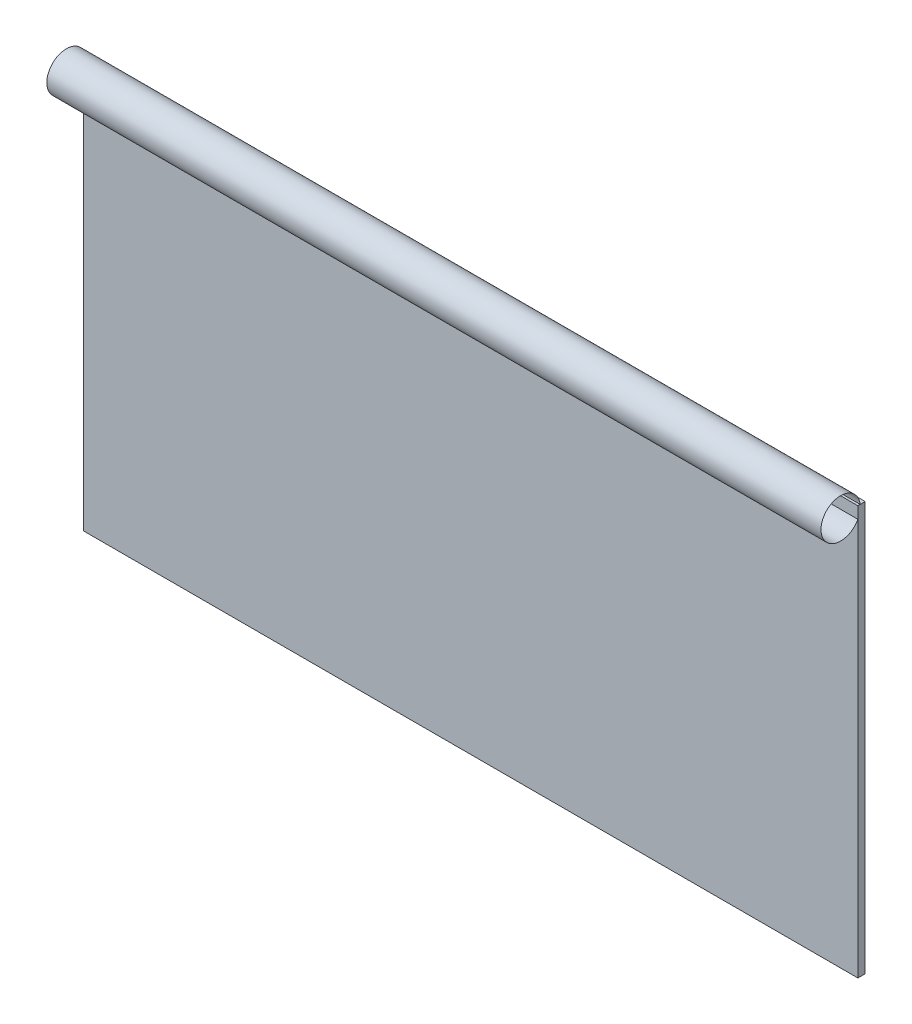
SolidWorks part; units mm, degrees
material "201 Annealed Stainless Steel (SS)"
ref_plane "Front Plane" through (0, 0, 0) normal (0, 0, 1) x (1, 0, 0)
ref_plane "Top Plane" through (0, 0, 0) normal (0, 1, 0) x (1, 0, 0)
ref_plane "Right Plane" through (0, 0, 0) normal (1, 0, 0) x (0, 0, -1)
sketch "Sketch1" plane through (0, 0, 0) normal (0, 0, 1) x (1, 0, 0)
  line L1 (-106, -56) -> (106, -56)
  line L2 (-106, -56) -> (-106, 56)
  line L3 (-106, 56) -> (106, 56)
  line L4 (106, -56) -> (106, 56)
  line L5 (-106, -56) -> (106, 56) construction
  line L6 (-106, 56) -> (106, -56) construction
  point P0 (0, 0)
  dimension "D1" = 212
  dimension "D2" = 112
extrude "Boss-Extrude1" add sketch "Sketch1" along normal blind 2
sketch "Sketch2" plane through (0, 0, 0) normal (0, 0, -1) x (-1, 0, 0)
  line L0 (61, 200) -> (61, -200) construction
  line L1 (-61, 314.7216) -> (-204.3993, 314.7216)
  line L2 (-61, 314.7216) -> (-61, -251.9618)
  line L3 (-61, -251.9618) -> (-204.3993, -251.9618)
  line L4 (-204.3993, 314.7216) -> (-204.3993, -251.9618)
  line L6 (61, 279.3211) -> (244.4765, 279.3211)
  line L7 (61, 279.3211) -> (61, -295.1839)
  line L8 (61, -295.1839) -> (244.4765, -295.1839)
  line L9 (244.4765, 279.3211) -> (244.4765, -295.1839)
  line L10 (-61, -200) -> (-61, -140) construction
extrude "Cut-Extrude1" [suppressed] cut sketch "Sketch2" against normal through all
sketch "Sketch3" plane through (106, 0, 0) normal (1, 0, 0) x (0, 0, -1)
  circle A0 centre (-6.722, 55.3681) radius 5.3835
surface "Surface-Extrude1" sketch "Sketch3"
sketch "Sketch4" plane through (-106, 0, 0) normal (-1, 0, 0) x (0, 0, 1)
  line L1 (2, 56) -> (0, 56) construction
  line L2 (0, -56) -> (0, 56) construction
  point P0 (10, 46)
  dimension "D1" = 10
  dimension "D2" = 10
ref_axis "Axis1" through (-106, 46, 10) along (1, 0, 0)
